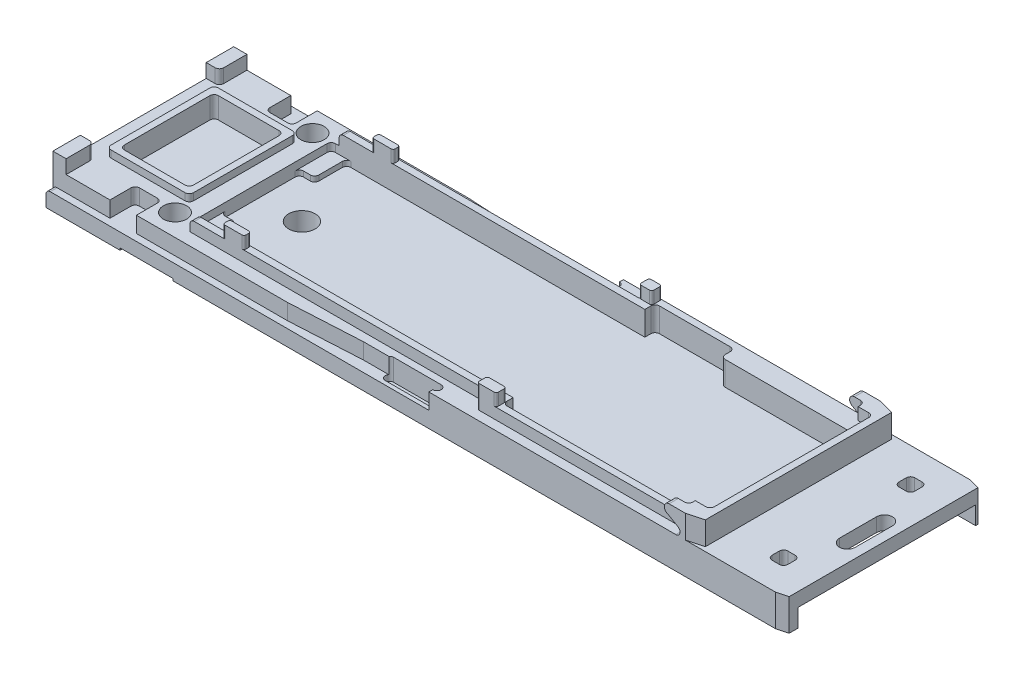
SolidWorks part; units mm, degrees
material "6063-T5"
ref_plane "Front Plane" through (0, 0, 0) normal (0, 0, 1) x (1, 0, 0)
ref_plane "Top Plane" through (0, 0, 0) normal (0, 1, 0) x (1, 0, 0)
ref_plane "Right Plane" through (0, 0, 0) normal (1, 0, 0) x (0, 0, -1)
sketch "Sketch1" plane through (0, 0, 0) normal (0, 1, 0) x (1, 0, 0)
  line L1 (-35, 9.2) -> (35, 9.2)
  line L2 (-35, 9.2) -> (-35, -9.2)
  line L3 (-35, -9.2) -> (35, -9.2)
  line L4 (35, 9.2) -> (35, -9.2)
  line L5 (-35, 9.2) -> (35, -9.2) construction
  line L6 (-35, -9.2) -> (35, 9.2) construction
  point P0 (0, 0)
  dimension "D1" = 70
  dimension "D2" = 18.4
extrude "Boss-Extrude1" add sketch "Sketch1" along normal blind 4.05
sketch "Sketch2" plane through (0, 4.05, 0) normal (0, 1, 0) x (1, 0, 0)
  line L0 (-35, 9.2) -> (-35, -9.2) construction
  line L1 (-23.95, 6.725) -> (-23.95, -6.725)
  line L2 (-23.95, -6.725) -> (6.7, -6.725)
  line L3 (6.7, -6.725) -> (6.7, -7.7)
  line L4 (6.7, -7.7) -> (26.3, -7.7)
  line L6 (26.3, -7.7) -> (26.3, 7.7)
  line L7 (26.3, 7.7) -> (5.7, 7.7)
  line L8 (5.7, 7.7) -> (5.7, 6.725)
  line L9 (5.7, 6.725) -> (-23.95, 6.725)
  line L10 (0, 0) -> (26.3, 0) construction
  dimension "D1" = 13.45
  dimension "D2" = 15.4
  dimension "D3" = 20.6
  dimension "D4" = 50.25
  dimension "D5" = 11.05
  dimension "D6" = 19.6
extrude "Cut-Extrude1" cut sketch "Sketch2" against normal blind 2.28
sketch "Sketch5" plane through (0, 4.05, 0) normal (0, 1, 0) x (1, 0, 0)
  line L0 (-23.95, 0) -> (-35, 0) construction
  line L1 (-32.75, 4.45) -> (-26.2, 4.45)
  line L2 (-32.75, 4.45) -> (-32.75, -4.45)
  line L3 (-32.75, -4.45) -> (-26.2, -4.45)
  line L4 (-26.2, 4.45) -> (-26.2, -4.45)
  line L5 (-32.75, 4.45) -> (-26.2, -4.45) construction
  line L6 (-32.75, -4.45) -> (-26.2, 4.45) construction
  line L7 (-23.95, 6.725) -> (-23.95, -6.725) construction
  line L8 (-35, 9.2) -> (-35, -9.2) construction
  point P0 (-29.475, 0)
  dimension "D1" = 8.9
  dimension "D2" = 6.55
extrude "Cut-Extrude2" cut sketch "Sketch5" against normal blind 2.38
sketch "Sketch17" plane through (0, 4.05, 0) normal (0, 1, 0) x (1, 0, 0)
  line L0 (-35, -9.2) -> (35, -9.2) construction
  line L1 (35, 9.2) -> (35, -9.2)
  line L2 (0, 0) -> (26.95, 0) construction
  line L4 (26.3, -7.7) -> (26.3, 7.7) construction
  line L5 (5.7, 7.7) -> (5.7, 6.725) construction
  line L11 (-35, 9.2) -> (35, 9.2)
  line L12 (-35, 9.2) -> (-35, -9.2)
  line L13 (-35, -9.2) -> (35, -9.2)
  line L14 (-23.2, 7.375) -> (-23.2, -7.375)
  line L57 (-23.2, -7.375) -> (5.05, -7.375)
  line L58 (5.05, -7.375) -> (5.05, -8.325)
  line L59 (5.05, -8.325) -> (26.95, -8.325)
  line L60 (26.95, -8.325) -> (26.95, 8.325)
  line L61 (26.95, 8.325) -> (5.05, 8.325)
  line L62 (5.05, 8.325) -> (5.05, 7.375)
  line L63 (5.05, 7.375) -> (-23.2, 7.375)
  dimension "D1" = 11.8
  dimension "D2" = 7.375
  dimension "D3" = 8.325
  dimension "D4" = 0.65
  dimension "D5" = 0.65
extrude "Cut-Extrude8" cut sketch "Sketch17" against normal blind 1.05
sketch "Sketch18" plane through (0, 0, 0) normal (0, 1, 0) x (1, 0, 0)
  line L10 (-32.75, 4.45) -> (-26.2, 4.45) construction
  line L11 (-26.2, -4.45) -> (-26.2, 4.45) construction
  line L12 (-32.75, -4.45) -> (-26.2, -4.45) construction
  line L13 (-32.75, 4.45) -> (-32.75, -4.45) construction
  line L14 (-33.375, 5.075) -> (-33.375, -5.075)
  line L15 (-33.375, -5.075) -> (-25.575, -5.075)
  line L16 (-25.575, -5.075) -> (-25.575, 5.075)
  line L17 (-25.575, 5.075) -> (-33.375, 5.075)
  line L18 (-33.375, 5.075) -> (-33.375, -5.075)
  line L19 (-33.375, -5.075) -> (-25.575, -5.075)
  line L20 (-25.575, -5.075) -> (-25.575, 5.075)
  line L21 (-25.575, 5.075) -> (-33.375, 5.075)
  line L22 (-32.75, 4.45) -> (-26.2, 4.45)
  line L23 (-26.2, -4.45) -> (-26.2, 4.45)
  line L24 (-32.75, -4.45) -> (-26.2, -4.45)
  line L25 (-32.75, 4.45) -> (-32.75, -4.45)
  dimension "D1" = 0.625
extrude "Boss-Extrude3" add sketch "Sketch18" along normal blind 3.67
hole_wizard "CSK for M2 Countersunk Flat Head Screw1" positions "Sketch7" profile "Sketch6" countersink size "M2" standard "ISO" end condition through all
sketch "Sketch7" plane through (-7.9019, 0, 3.8056) normal (0, 1, 0) x (-1, 0, 0)
  line L0 (-7.9019, -3.8056) -> (27.0981, -3.8056) construction
  line L1 (27.0981, -13.0056) -> (27.0981, 5.3944) construction
  line L4 (27.0981, 5.3944) -> (27.0981, -13.0056) construction
  point P0 (17.5981, -10.3056)
  point P1 (17.5981, 2.6944)
  dimension "D1" = 13
  dimension "D2" = 9.5
sketch "Sketch6" plane through (-25.5, 0, -6.5) normal (1, 0, 0) x (0, 0, -1)
  line L0 (0, 0) -> (0, 4.05)
  line L1 (0, 4.05) -> (1.1, 4.05)
  line L2 (1.1, 4.05) -> (1.1, 1.3)
  line L3 (1.1, 1.3) -> (2.2, 0.2)
  line L4 (2.2, 0.2) -> (2.2, 0)
  line L6 (2.2, 0) -> (0, 0)
  line L7 (-1.1, 1.3) -> (-2.2, 0.2) construction
  line L11 (0, -6.35) -> (0, 107.95) construction
  dimension "Thru Hole Dia." = 2.2
  dimension "Thru Hole Depth" = 4.05
  dimension "C'Sink Dia." = 4.4
  dimension "C'Sink Angle" = 90
  dimension "Head Clearance" = 0.2
sketch "Sketch13" plane through (0, 4.05, 0) normal (0, 1, 0) x (1, 0, 0)
  line L0 (-35, 9.2) -> (1.2, 9.2)
  line L1 (35, 9.2) -> (35, -9.2) construction
  line L2 (1.2, 9.2) -> (1.2, 8.175)
  line L3 (1.2, 8.175) -> (-6, 8.175)
  line L4 (-6, 8.175) -> (-12.8, 8.55)
  line L5 (-12.8, 8.55) -> (-35, 8.55)
  line L6 (-35, 8.55) -> (-35, 9.2)
  line L10 (35, 9.2) -> (-35, 9.2) construction
  line L11 (-35, 9.2) -> (-35, -9.2) construction
  dimension "D1" = 8.175
  dimension "D2" = 33.8
  dimension "D3" = 7.2
  dimension "D4" = 6.8
  dimension "D5" = 0.65
extrude "Cut-Extrude5" cut sketch "Sketch13" against normal offset from surface (2.55 mm away) 1.5 up to face at (-25.5, 0, -8.7)
sketch "Sketch19" plane through (0, 0, 0) normal (0, 1, 0) x (1, 0, 0)
  line L1 (-35, 8.55) -> (-33.75, 8.55)
  line L2 (-35, 8.55) -> (-35, 5.95)
  line L3 (-35, 5.95) -> (-33.75, 5.95)
  line L4 (-33.75, 8.55) -> (-33.75, 5.95)
  dimension "D1" = 2.6
  dimension "D2" = 1.25
extrude "Boss-Extrude4" add sketch "Sketch19" along normal blind 4.3
sketch "Sketch20" plane through (0, 3, 0) normal (0, 1, 0) x (1, 0, 0)
  line L0 (-33.75, 8.55) -> (-12.8, 8.55) construction
  line L1 (-29.6, 8.55) -> (-27.1, 8.55)
  line L2 (-29.6, 8.55) -> (-29.6, 6.165)
  line L3 (-29.6, 6.165) -> (-27.1, 6.165)
  line L4 (-27.1, 8.55) -> (-27.1, 6.165)
  line L5 (-35, -9.2) -> (-35, 5.95) construction
  dimension "D1" = 2.5
  dimension "D2" = 6.165
  dimension "D3" = 5.4
extrude "Cut-Extrude9" cut sketch "Sketch20" against normal up to surface (1.5 mm away) up to face at (-14.4, 1.5, -8.6417)
sketch "Sketch21" plane through (0, 0, 0) normal (0, 1, 0) x (1, 0, 0)
  line L0 (5.05, 7.375) -> (-23.2, 7.375) construction
  line L1 (-20.1, 7.375) -> (-18.1, 7.375)
  line L2 (-20.1, 7.375) -> (-20.1, 6.725)
  line L3 (-20.1, 6.725) -> (-18.1, 6.725)
  line L4 (-18.1, 7.375) -> (-18.1, 6.725)
  line L5 (5.7, 6.725) -> (-23.95, 6.725) construction
  line L6 (-23.2, 7.375) -> (-23.2, 6.725) construction
  dimension "D1" = 2
  dimension "D2" = 5.1
extrude "Boss-Extrude5" add sketch "Sketch21" along normal blind 5.2
sketch "Sketch22" plane through (0, 0, 0) normal (0, -1, 0) x (1, 0, 0)
  line L0 (24.9, -7.7) -> (26.95, -7.7)
  line L1 (26.3, -7.7) -> (5.7, -7.7) construction
  line L2 (26.95, -8.325) -> (26.95, 8.325) construction
  line L3 (26.95, -7.7) -> (26.95, -9.2)
  line L4 (1.2, -9.2) -> (35, -9.2) construction
  line L5 (26.95, -9.2) -> (22.15, -9.2)
  line L6 (22.15, -9.2) -> (22.15, -8.325)
  line L7 (5.05, -8.325) -> (26.95, -8.325) construction
  line L8 (22.15, -8.325) -> (24.9, -8.325)
  line L9 (24.9, -8.325) -> (24.9, -7.7)
  dimension "D1" = 4.8
  dimension "D2" = 2.05
extrude "Boss-Extrude6" add sketch "Sketch22" against normal blind 5.2
chamfer "Chamfer2" distance 1.5 angle 15 1 edges at (26.95, 4.1, -9.2)
chamfer "Chamfer1" distance 1 angle 15 2 edges at (35, 1.5, -9.2) (35, 1.5, 9.2)
sketch "Sketch25" plane through (0, 3, 0) normal (0, 1, 0) x (1, 0, 0)
  line L1 (31.2, 6.75) -> (31.9, 6.75)
  line L2 (30.8, 6.35) -> (30.8, 5.65)
  line L3 (31.2, 5.25) -> (31.9, 5.25)
  line L4 (32.3, 6.35) -> (32.3, 5.65)
  line L5 (30.8, 6.75) -> (32.3, 5.25) construction
  line L6 (30.8, 5.25) -> (32.3, 6.75) construction
  line L7 (35, -8.9321) -> (35, 8.9321) construction
  arc A0 (31.9, 6.75) -> (32.3, 6.35) centre (31.9, 6.35) cw
  arc A1 (32.3, 5.65) -> (31.9, 5.25) centre (31.9, 5.65) cw
  arc A2 (31.2, 5.25) -> (30.8, 5.65) centre (31.2, 5.65) cw
  arc A3 (30.8, 6.35) -> (31.2, 6.75) centre (31.2, 6.35) cw
  point P0 (31.55, 6)
  dimension "D5" = 0.4
  dimension "D1" = 1.5
  dimension "D2" = 1.5
  dimension "D3" = 6
  dimension "D4" = 4.2
extrude "Cut-Extrude10" cut sketch "Sketch25" against normal through all
sketch "Sketch16" plane through (0, 0, 0) normal (0, -1, 0) x (1, 0, 0)
  line L0 (-28, -9.2) -> (-28, -6.5)
  line L2 (-23, -6.5) -> (-23, -9.2)
  line L3 (-23, -9.2) -> (-28, -9.2)
  line L4 (34, -9.2) -> (-35, -9.2) construction
  arc A0 (-28, -6.5) -> (-23, -6.5) centre (-25.5, -6.5) cw
  circle A1 centre (-25.5, -6.5) radius 2.2 construction
  dimension "D1" = 5
extrude "Cut-Extrude7" cut sketch "Sketch16" against normal blind 0.2
mirror "Mirror1" about plane through (0, 0, 0) normal (0, 0, 1) of "Cut-Extrude10", "Boss-Extrude5", "Cut-Extrude9", "Boss-Extrude4", "Cut-Extrude5", "Cut-Extrude7", "Boss-Extrude6", "Chamfer2"
sketch "Sketch29" plane through (0, 0, -9.2) normal (0, 0, 1) x (1, 0, 0)
  line L0 (23.6939, 4.3603) -> (24.7572, 3.7464)
  line L1 (24.6572, 3.7464) -> (23.6689, 4.317) construction
  line L2 (24.5572, 3) -> (21.5572, 3)
  line L3 (34, 3) -> (25.45, 3) construction
  line L5 (22.15, 5.2) -> (25.45, 5.2) construction
  line L6 (23.9189, 5.2) -> (21.5572, 5.2)
  line L7 (21.5572, 5.2) -> (21.5572, 3)
  arc A0 (24.7572, 3.7464) -> (24.5572, 3) centre (24.5572, 3.4) cw
  arc A1 (23.6939, 4.3603) -> (23.9189, 5.2) centre (23.9189, 4.75) cw
  arc A2 (23.9189, 5.25) -> (23.6689, 4.317) centre (23.9189, 4.75) ccw construction
  dimension "D2" = 3
  dimension "D1" = 0.4
extrude "Cut-Extrude12" cut sketch "Sketch29" along normal up to surface (0.875 mm away) up to face at (23.525, 4.625, -8.325)
sketch "Sketch30" plane through (0, 0, 9.2) normal (0, 0, 1) x (1, 0, 0)
  line L0 (23.6939, 4.3603) -> (24.7572, 3.7464)
  line L1 (24.5572, 3) -> (21.5572, 3)
  line L2 (22.15, 5.2) -> (25.45, 5.2) construction
  line L3 (23.9189, 5.2) -> (21.5572, 5.2)
  line L4 (21.5572, 5.2) -> (21.5572, 3)
  line L6 (1.2, 3) -> (22.15, 3) construction
  line L7 (24.7572, 3.7464) -> (24.2313, 4.05) construction
  arc A0 (24.7572, 3.7464) -> (24.5572, 3) centre (24.5572, 3.4) cw
  arc A1 (23.9189, 5.2) -> (23.6939, 4.3603) centre (23.9189, 4.75) ccw construction
  arc A2 (23.6939, 4.3603) -> (23.9189, 5.2) centre (23.9189, 4.75) cw
  dimension "D1" = 3
  dimension "D3" = 0.4
extrude "Cut-Extrude13" cut sketch "Sketch30" against normal up to surface (0.875 mm away) up to face at (23.525, 4.625, 8.325)
sketch "Sketch26" plane through (0, 0, 0) normal (0, -1, 0) x (1, 0, 0)
  line L0 (5.05, 7.375) -> (-23.2, 7.375) construction
  line L1 (6.7, 8.325) -> (4.9, 8.325)
  line L2 (6.7, 8.325) -> (6.7, 7.375)
  line L3 (6.7, 7.375) -> (4.9, 7.375)
  line L4 (4.9, 8.325) -> (4.9, 7.375)
  line L5 (5.05, -7.375) -> (-18.1, -7.375) construction
  line L6 (5.7, -8.325) -> (4.52, -8.325)
  line L7 (5.7, -8.325) -> (5.7, -7.375)
  line L8 (5.7, -7.375) -> (4.52, -7.375)
  line L9 (4.52, -8.325) -> (4.52, -7.375)
  line L10 (6.7, 6.725) -> (6.7, 7.7) construction
  line L12 (24.5572, 8.325) -> (5.05, 8.325) construction
  line L13 (5.7, -7.7) -> (5.7, -6.725) construction
  line L14 (5.05, -8.325) -> (24.5572, -8.325) construction
  dimension "D1" = 1.8
  dimension "D2" = 1.18
extrude "Boss-Extrude8" add sketch "Sketch26" against normal blind 5.2
fillet "Fillet1" radius 0.4 2 edges at (-23.2, 4.05, 7.05) (-23.2, 4.05, -7.05)
fillet "Fillet2" radius 0.2 16 edges at (-18.1, 4.625, -6.725) (-20.1, 4.625, -6.725) (-20.1, 4.625, -7.375) (-18.1, 4.625, -7.375) (-18.1, 4.625, 6.725) (-18.1, 4.625, 7.375) (-20.1, 4.625, 6.725) (-20.1, 4.625, 7.375) (5.7, 4.625, -7.375) (4.52, 4.625, -7.375) (5.7, 4.625, -8.325) (4.52, 4.1, -8.325) (6.7, 4.625, 8.325) (4.9, 4.1, 8.325) (4.9, 4.625, 7.375) (6.7, 4.625, 7.375)
sketch "Sketch23" plane through (0, 4.05, 0) normal (0, 1, 0) x (1, 0, 0)
  line L4 (26.3, 7.7) -> (26.3, -7.7)
  line L5 (26.3, -7.7) -> (26.95, -7.7)
  line L6 (26.95, -7.7) -> (26.95, 7.7)
  line L7 (26.95, 7.7) -> (26.3, 7.7)
  line L8 (26.3, 7.7) -> (26.3, -7.7)
  line L9 (26.3, -7.7) -> (26.95, -7.7)
  line L10 (26.95, -7.7) -> (26.95, 7.7)
  line L11 (26.95, 7.7) -> (26.3, 7.7)
  dimension "D1" = 0
extrude "Boss-Extrude7" add sketch "Sketch23" along normal up to surface (1.15 mm away) up to face at (25.284, 5.2, -8.464)
sketch "Sketch27" plane through (0, 1.77, 0) normal (0, 1, 0) x (1, 0, 0)
  line L0 (26.3, 7.7) -> (5.7, 7.7) construction
  line L1 (13.2, 7.7) -> (26.3, 7.7)
  line L2 (13.2, 7.7) -> (13.2, 6.425)
  line L3 (13.2, 6.425) -> (26.3, 6.425)
  line L4 (26.3, 7.7) -> (26.3, 6.425)
  line L5 (26.3, -7.7) -> (26.3, 7.7) construction
  line L6 (24.2313, 8.325) -> (5.5, 8.325) construction
  line L7 (5.7, 7.7) -> (5.7, 6.725) construction
  dimension "D1" = 1.9
  dimension "D2" = 7.5
extrude "Boss-Extrude9" add sketch "Sketch27" along normal up to surface (2.28 mm away) up to face at (-4.2057, 4.05, -7.2117)
fillet "Fillet3" radius 0.4 2 edges at (13.2, 2.91, -7.7) (13.2, 2.91, -6.425)
sketch "Sketch28" plane through (0, 0, 0) normal (0, -1, 0) x (1, 0, 0)
  line L1 (35, 8.1) -> (30.8, 8.1)
  line L2 (35, 8.1) -> (35, -8.7)
  line L3 (35, 0) -> (0, 0) construction
  line L4 (30.8, 8.1) -> (30.8, -7)
  line L5 (30.8, 6.35) -> (30.8, 5.65) construction
  line L6 (35, -8.7) -> (14.2, -8.7)
  line L8 (30.8, -7) -> (14.2, -7)
  line L9 (14.2, -8.7) -> (14.2, -7)
  line L10 (34, -9.2) -> (-23, -9.2) construction
  line L11 (35, 8.9321) -> (35, -8.9321) construction
  line L12 (-23, 9.2) -> (34, 9.2) construction
  dimension "D1" = 2.2
  dimension "D2" = 0.5
  dimension "D3" = 1.1
  dimension "D4" = 16.6
extrude "Cut-Extrude11" cut sketch "Sketch28" against normal blind 1.7
sketch "Sketch31" plane through (0, 1.77, 0) normal (0, 1, 0) x (1, 0, 0)
  line L1 (-23.95, 6.725) -> (-22.5, 6.725)
  line L2 (-23.95, 6.725) -> (-23.95, 3.7)
  line L3 (-23.95, 3.7) -> (-22.5, 3.7)
  line L4 (-22.5, 6.725) -> (-22.5, 3.7)
  line L5 (-23.95, -6.725) -> (-22.5, -6.725)
  line L6 (-23.95, -6.725) -> (-23.95, -3.7)
  line L7 (-23.95, -3.7) -> (-22.5, -3.7)
  line L8 (-22.5, -6.725) -> (-22.5, -3.7)
  dimension "D1" = 7.4
  dimension "D2" = 1.45
extrude "Boss-Extrude10" add sketch "Sketch31" along normal blind 0.5
sketch "Sketch32" plane through (0, 1.5, 0) normal (0, 1, 0) x (1, 0, 0)
  line L1 (1.2, 8.175) -> (-3.3, 8.175)
  line L2 (1.2, 8.175) -> (1.2, 8.825)
  line L3 (1.2, 8.825) -> (-3.3, 8.825)
  line L4 (-3.3, 8.175) -> (-3.3, 8.825)
  line L5 (1.2, -8.175) -> (-3.3, -8.175)
  line L6 (1.2, -8.175) -> (1.2, -8.825)
  line L7 (1.2, -8.825) -> (-3.3, -8.825)
  line L8 (-3.3, -8.175) -> (-3.3, -8.825)
  dimension "D1" = 4.5
  dimension "D2" = 0.65
extrude "Cut-Extrude14" cut sketch "Sketch32" against normal blind 0.55
sketch "Sketch33" plane through (0, 0.95, 0) normal (0, 1, 0) x (1, 0, 0)
  line L1 (-3.3, -8.825) -> (1.2, -8.825)
  line L2 (1.2, -8.175) -> (1.2, -9.2) construction
  line L3 (-3.3, -8.025) -> (1.2, -8.025)
  arc A0 (-3.3, -8.025) -> (-3.3, -8.825) centre (-3.3, -8.425) ccw
  arc A1 (1.2, -8.025) -> (1.2, -8.825) centre (1.2, -8.425) cw
  dimension "D1" = 0.8
extrude "Cut-Extrude15" cut sketch "Sketch33" along normal through all
mirror "Mirror2" about plane through (0, 0, 0) normal (0, 0, 1) of "Cut-Extrude15"
fillet "Fillet5" radius 0.4 24 edges at (5.7, 2.91, -7.7) (26.3, 3.485, 7.7) (6.7, 2.91, 7.7) (-29.6, 2.25, -6.165) (-27.1, 2.25, -6.165) (24.9, 4.625, -8.325) (-27.1, 2.25, 6.165) (-29.6, 2.25, 6.165) (-26.2, 2.67, -4.45) (-26.2, 2.67, 4.45) (-32.75, 2.67, 4.45) (-32.75, 2.67, -4.45) (24.9, 4.625, 8.325) (26.3, 4.625, -7.7) (26.3, 2.91, -6.425) (14.2, 0.85, -8.7) (14.2, 0.85, -7) (30.8, 0.85, 8.1) (-23.95, 2.635, -6.725) (-23.95, 2.02, -3.7) (-22.5, 2.02, -6.725) (-23.95, 2.635, 6.725) (-23.95, 2.02, 3.7) (-22.5, 2.02, 6.725)
fillet "Fillet6" radius 0.4 2 edges at (-22.5, 2.02, -3.7) (-22.5, 2.02, 3.7)
fillet "Fillet7" radius 0.4 2 edges at (-35, 1.5, -8.875) (-35, 1.5, 8.875)
fillet "Fillet8" radius 0.4 6 edges at (-33.75, 3.65, -5.95) (-33.75, 3.65, 5.95) (-33.375, 3.335, -5.075) (-25.575, 3.335, -5.075) (-33.375, 3.335, 5.075) (-25.575, 3.335, 5.075)
sketch "Sketch34" plane through (0, 3, 0) normal (0, 1, 0) x (1, 0, 0)
  line L0 (33.3382, -1.75) -> (33.3382, 1.75) construction
  line L1 (32.5882, -1.75) -> (32.5882, 1.75)
  line L2 (34.0882, -1.75) -> (34.0882, 1.75)
  arc A0 (32.5882, -1.75) -> (34.0882, -1.75) centre (33.3382, -1.75) ccw
  arc A1 (34.0882, 1.75) -> (32.5882, 1.75) centre (33.3382, 1.75) ccw
  point P2 (33.3382, 0)
  dimension "D1" = 1.5
  dimension "D2" = 3.5
extrude "Cut-Extrude16" cut sketch "Sketch34" against normal through all
sketch "Sketch35" plane through (0, 1.77, 0) normal (0, 1, 0) x (1, 0, 0)
  circle A0 centre (-20, 0) radius 1.25
  point P2 (0, 0)
  dimension "D1" = 2.5
  dimension "D2" = 20
extrude "Cut-Extrude17" cut sketch "Sketch35" against normal through all
